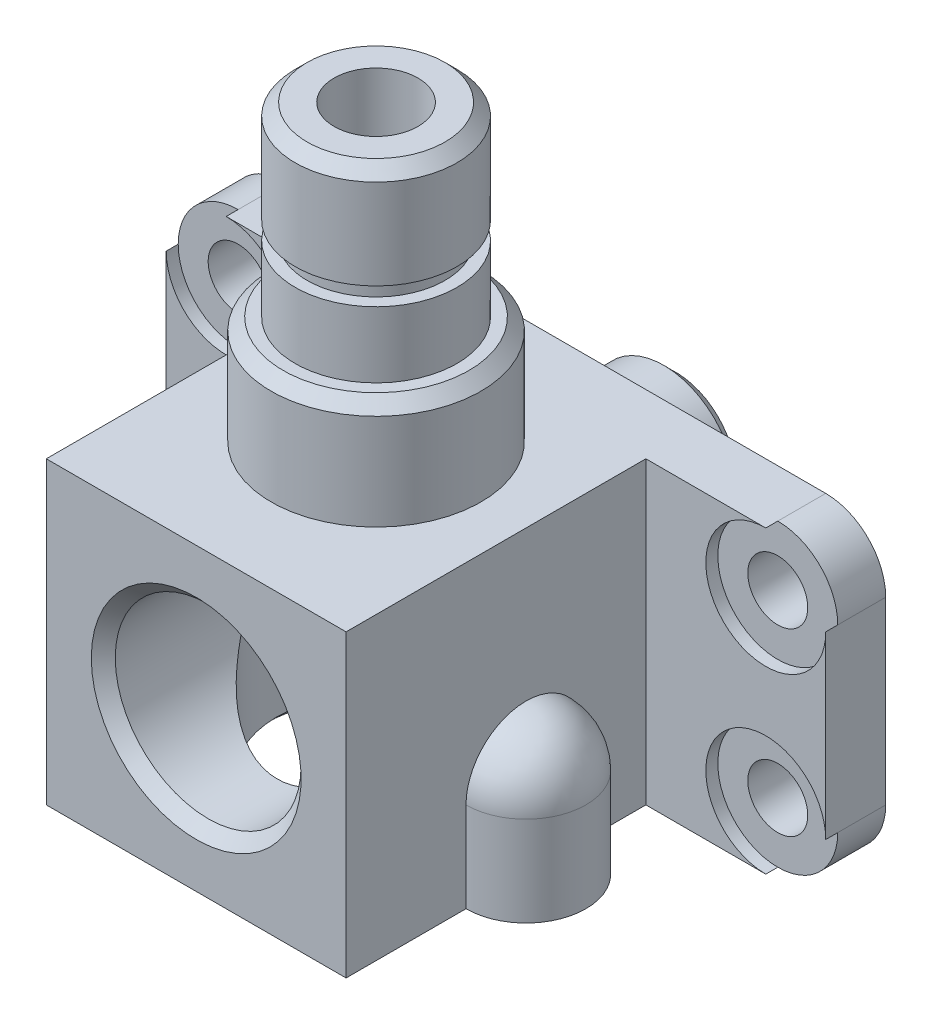
SolidWorks part; units mm, degrees
ref_plane "Front Plane" through (0, 0, 0) normal (1, 0, 0) x (0, 1, 0)
ref_plane "Top Plane" through (0, 0, 0) normal (0, 0, 1) x (0, 1, 0)
ref_plane "Right Plane" through (0, 0, 0) normal (0, 1, 0) x (-1, 0, 0)
sketch "Sketch1" plane through (0, 0, 0) normal (0, 0, 1) x (0, 1, 0)
  line L1 (-25, -55) -> (25, -55)
  line L2 (-25, -55) -> (-25, 55)
  line L3 (-25, 55) -> (25, 55)
  line L4 (25, -55) -> (25, 55)
  line L5 (-25, -55) -> (25, 55) construction
  line L6 (-25, 55) -> (25, -55) construction
  point P0 (0, 0)
  dimension "D1" = 110
  dimension "D2" = 50
extrude "Boss-Extrude1" add sketch "Sketch1" along normal blind 10
fillet "Fillet1" radius 10 4 edges at (-55, 25, 5) (-55, -25, 5) (55, -25, 5) (55, 25, 5)
sketch "Sketch3" plane through (0, 0, 0) normal (0, 0, 1) x (0, 1, 0)
  line L0 (25, -45) -> (25, 45) construction
  line L1 (-25, -25) -> (25, -25)
  line L2 (-25, -25) -> (-25, 25)
  line L3 (-25, 25) -> (25, 25)
  line L4 (25, -25) -> (25, 25)
  line L5 (-25, -25) -> (25, 25) construction
  line L6 (-25, 25) -> (25, -25) construction
  point P0 (0, 0)
  dimension "D1" = 50
extrude "Boss-Extrude2" add sketch "Sketch3" along normal blind 60
sketch "Sketch4" plane through (0, 0, 0) normal (0, 0, -1) x (1, 0, 0)
  circle A0 centre (0, 0) radius 14
  dimension "D1" = 28
extrude "Boss-Extrude3" add sketch "Sketch4" along normal blind 12
sketch "Sketch5" plane through (0, 0, 0) normal (0, 0, -1) x (1, 0, 0)
  circle A0 centre (0, 0) radius 12
  dimension "D1" = 24
extrude "Boss-Extrude4" add sketch "Sketch5" along normal blind 20
ref_plane "Plane2" through (0, 0, 30) normal (0, 0, 1) x (0, 1, 0)
sketch "Sketch7" plane through (0, 0, 30) normal (0, 0, 1) x (0, 1, 0)
  line L0 (0, 0) -> (50000, 0) construction
  line L1 (25, 17.5) -> (43, 17.5)
  line L2 (25, -25) -> (25, 25) construction
  line L3 (43, 17.5) -> (43, 13.5)
  line L4 (43, 13.5) -> (54, 13.5)
  line L5 (54, 13.5) -> (54, 11.5)
  line L7 (74, 13.5) -> (74, 0)
  line L8 (74, 0) -> (25, 0)
  line L9 (25, 0) -> (25, 17.5)
  line L10 (57, 11.5) -> (57, 13.5)
  line L11 (57, 13.5) -> (74, 13.5)
  line L13 (54, 11.5) -> (57, 11.5)
  point P16 (57, 11.5)
  point P17 (60.2694, 11.5)
  point P18 (57, 11.5)
  point P19 (0, 0)
  point P20 (0, 0)
  point P21 (74, 13.0979)
  dimension "D1" = 74
  dimension "D2" = 20
  dimension "D3" = 31
  dimension "D4" = 27
  dimension "D5" = 35
  dimension "D6" = 2
  dimension "D7" = 3
revolve "Revolve1" add sketch "Sketch7" angle 360 about L0
cosmetic thread "Cosmetic Thread2" parameters "D2"=23.704
hole_wizard "Hole1" positions "Sketch10" profile "Sketch11" legacy end condition through all
sketch "Sketch10" plane through (0, 0, 10) normal (0, 0, 1) x (1, 0, 0)
  line L0 (0, 0) -> (50000, 0) construction
  line L1 (0, 0) -> (0, 50000) construction
  point P0 (-45, -15)
  point P2 (-45, 15)
  point P12 (0, 0)
  dimension "D1" = 30
  dimension "D2" = 90
sketch "Sketch11" plane through (-45, -15, 10) normal (1, 0, 0) x (0, -1, 0)
  line L0 (0, 0) -> (0, 29.5804)
  line L1 (0, 29.5804) -> (5, 29.5804)
  line L2 (5, 29.5804) -> (5, 2)
  line L3 (5, 2) -> (10, 2)
  line L4 (10, 2) -> (10, 0)
  line L5 (10, 0) -> (0, 0)
  line L6 (0, 110) -> (0, -10) construction
  dimension "Diameter" = 10
  dimension "Depth" = 30
  dimension "C-Bore Diameter" = 20
  dimension "C-Bore Depth" = 2
mirror "Mirror1" about plane through (0, 0, 0) normal (1, 0, 0) of "Hole1"
sketch "Sketch12" plane through (0, 0, 30) normal (0, 0, 1) x (0, 1, 0)
  line L0 (-25, 35) -> (-10, 35)
  line L2 (-25, 45) -> (-25, 25) construction
  line L3 (25, 25) -> (-25, 25) construction
  line L4 (0, 0) -> (0, 50000) construction
  line L5 (0, 25) -> (-25, 25)
  line L6 (-25, 25) -> (-25, 35)
  arc A2 (-10, 35) -> (0, 25) centre (-10, 25) cw
revolve "Revolve2" add sketch "Sketch12" angle 360 about L5
mirror "Mirror2" about plane through (0, 0, 0) normal (1, 0, 0) of "Revolve2"
hole_wizard "Hole2" positions "Sketch14" profile "Sketch13" legacy end condition through all
sketch "Sketch14" plane through (0, -25, 0) normal (0, -1, 0) x (1, 0, 0)
  point P0 (0, 30)
  point P3 (0, 0)
  dimension "D1" = 30
sketch "Sketch13" plane through (0, -25, 30) normal (1, 0, 0) x (0, 0, -1)
  line L0 (0, 0) -> (0, 99)
  line L1 (0, 99) -> (7, 99)
  line L2 (7, 99) -> (7, 44)
  line L3 (7, 44) -> (16.5, 44)
  line L4 (16.5, 44) -> (16.5, 0)
  line L5 (16.5, 0) -> (0, 0)
  line L6 (0, 110) -> (0, -10) construction
  dimension "Diameter" = 14
  dimension "Depth" = 99
  dimension "C-Bore Diameter" = 33
  dimension "C-Bore Depth" = 44
hole_wizard "M10 Tapped Hole1" positions "Sketch15" profile "Sketch16" tap size "M10" standard "ISO"
sketch "Sketch15" plane through (0, -25, 0) normal (0, -1, 0) x (-1, 0, 0)
  arc A0 (25, -40) -> (25, -20) centre (25, -30) ccw construction
  arc A1 (25, -40) -> (25, -20) centre (25, -30) ccw construction
  point P2 (25, -30)
  point P8 (0, 0)
  point P9 (0, 0)
sketch "Sketch16" plane through (-25, -25, 30) normal (1, 0, 0) x (0, 0, -1)
  line L0 (0, 0) -> (0, 17.5537)
  line L1 (0, 17.5537) -> (4.25, 15)
  line L2 (4.25, 15) -> (4.25, 0)
  line L5 (4.25, 0) -> (0, 0)
  line L10 (0, 17.5537) -> (-4.25, 15) construction
  line L11 (0, -6.35) -> (0, 107.95) construction
  dimension "Tap Drill Dia." = 8.5
  dimension "Tap Drill Depth" = 15
  dimension "Drill Angle" = 118
cosmetic thread "Hole Thread1" parameters "D1"=12, "D2"=10
mirror "Mirror4" about plane through (0, 0, 0) normal (1, 0, 0) of "M10 Tapped Hole1"
cosmetic thread "Hole Thread3" parameters "D1"=12, "D2"=10
hole_wizard "M33x2.0 Tapped Hole1" positions "Sketch23" profile "Sketch24" tap size "M33x2.0" standard "ISO" end condition up to next
sketch "Sketch23" plane through (0, 0, 60) normal (0, 0, 1) x (1, 0, 0)
  point P0 (0, 0)
sketch "Sketch24" plane through (0, 0, 60) normal (1, 0, 0) x (0, -1, 0)
  line L0 (0, 0) -> (0, 13.5)
  line L1 (0, 13.5) -> (15.5, 13.5)
  line L2 (15.5, 13.5) -> (15.5, 0)
  line L5 (15.5, 0) -> (0, 0)
  line L11 (0, -6.35) -> (0, 107.95) construction
  dimension "Thru Tap Drill Dia." = 31
  dimension "Thru Tap Drill Depth" = 13.5
cosmetic thread "Hole Thread4" parameters "D2"=33
hole_wizard "Hole4" positions "Sketch25" profile "Sketch26" legacy end condition through all
sketch "Sketch25" plane through (0, 0, 30) normal (0, 0, 1) x (0, 1, 0)
  point P0 (0, 0)
sketch "Sketch26" plane through (0, 0, 30) normal (1, 0, 0) x (0, -1, 0)
  line L0 (0, 0) -> (0, 50)
  line L1 (0, 50) -> (9, 50)
  line L2 (9, 50) -> (9, 22)
  line L3 (9, 22) -> (15, 22)
  line L4 (15, 22) -> (15, 0)
  line L5 (15, 0) -> (0, 0)
  line L6 (0, 110) -> (0, -10) construction
  dimension "Diameter" = 18
  dimension "Depth" = 50
  dimension "C-Bore Diameter" = 30
  dimension "C-Bore Depth" = 22
chamfer "Chamfer3" distance 2 angle 45 6 edges at (15.5, 0, 60) (0, -25, 13.5) (-12, 0, -20) (-14, 0, -12) (0, 43, 12.5) (0, 74, 16.5)
